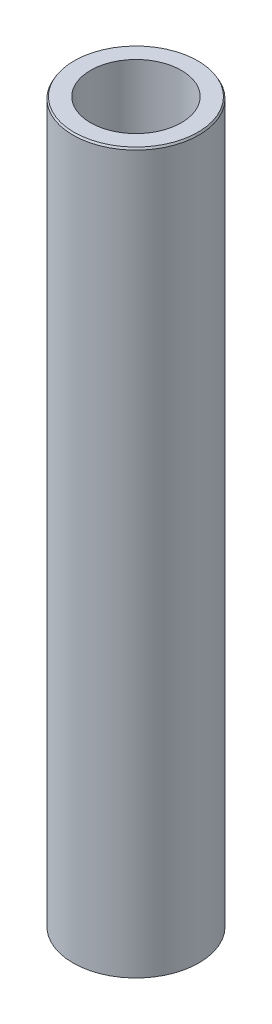
SolidWorks part; units mm, degrees
ref_plane "Front Plane" through (0, 0, 0) normal (0, 0, 1) x (1, 0, 0)
ref_plane "Top Plane" through (0, 0, 0) normal (0, 1, 0) x (1, 0, 0)
ref_plane "Right Plane" through (0, 0, 0) normal (1, 0, 0) x (0, 0, -1)
sketch "Sketch1" plane through (0, 0, 0) normal (0, 1, 0) x (1, 0, 0)
  circle A0 centre (0, 0) radius 52.5
  dimension "SHAFT_OD" = 105
extrude "Boss-Extrude1" add sketch "Sketch1" along normal blind 600
sketch "Sketch2" plane through (0, 0, 0) normal (0, 1, 0) x (1, 0, 0)
  circle A0 centre (0, 0) radius 37.8592
  dimension "BORE_D" = 75.7183
extrude "Cut-Extrude1" cut sketch "Sketch2" along normal through all
chamfer "Chamfer1" distance 1.5731 angle 30 2 edges at (0, 600, 52.5) (0, 0, 52.5) first distance on face at (0, 600, 52.5) first distance on face at (0, 0, 37.8592)
